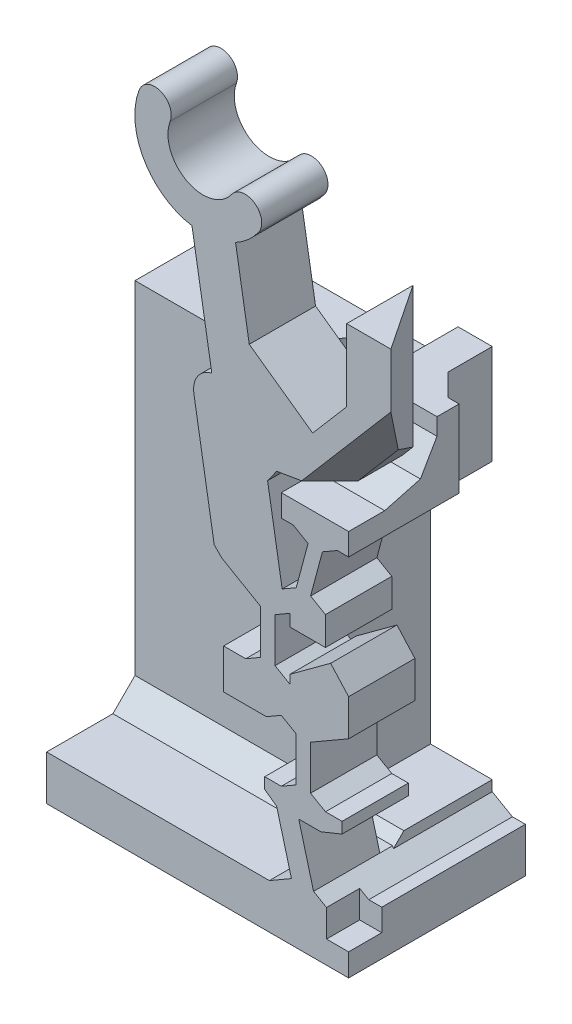
SolidWorks part; units mm, degrees
material "Nylon 6/12"
ref_plane "Front Plane" through (0, 0, 0) normal (0, 0, 1) x (1, 0, 0)
ref_plane "Top Plane" through (0, 0, 0) normal (0, 1, 0) x (1, 0, 0)
ref_plane "Right Plane" through (0, 0, 0) normal (1, 0, 0) x (0, 0, -1)
sketch "Sketch-SkeletonConfigUp" plane through (0, 0, 0) normal (0, 0, 1) x (1, 0, 0)
  line L0 (0, 0) -> (0, -50000) construction
  line L1 (0, 0) -> (4.5811, 6.2164) construction
  line L2 (9.8143, 13.3177) -> (4.5811, 13.945) construction
  line L3 (4.5811, 13.945) -> (2.9713, 10.4094) construction
  line L4 (2.9713, 10.4094) -> (4.5811, 6.2164) construction
  line L5 (4.5811, 13.945) -> (6.2429, 19.1409) construction
  line L6 (2.9713, 10.4094) -> (0.0405, 27.8193) construction
  line L7 (4.5811, 6.2164) -> (9.8143, 13.3177) construction
  line L8 (-587.3593, -797.0242) -> (9.8143, 13.3177) construction
  dimension "D2" = 7.7221
  dimension "D3" = 8.8212
  dimension "D4" = 5.2707
  dimension "D5" = 119.553
  dimension "D6" = 3.8848
  dimension "D7" = 5.4552
  dimension "D8" = 17.6549
  dimension "D9" = 4.4914
  dimension "D10" = 6.745
  dimension "D11" = 145.964
  dimension "D12" = 143.612
sketch "Sketch-SkeletonConfigDown" plane through (0, 0, 0) normal (0, 0, 1) x (1, 0, 0)
  line L0 (0, 0) -> (0, -50000) construction
  line L1 (0, 0) -> (4.5811, 6.2164) construction
  line L2 (9.8143, 13.3177) -> (4.5811, 13.945) construction
  line L3 (4.5811, 13.945) -> (6.1909, 10.4094) construction
  line L4 (6.1909, 10.4094) -> (4.5811, 6.2164) construction
  line L5 (4.5811, 13.945) -> (1.753, 18.6098) construction
  line L6 (6.1909, 10.4094) -> (-8.8652, 19.6294) construction
  line L7 (4.5811, 6.2164) -> (9.8143, 13.3177) construction
  line L8 (-589.9357, -800.5203) -> (9.8143, 13.3177) construction
  dimension "D2" = 7.7221
  dimension "D3" = 8.8212
  dimension "D4" = 5.2707
  dimension "D5" = 119.553
  dimension "D6" = 3.8848
  dimension "D7" = 5.4552
  dimension "D8" = 17.6549
  dimension "D9" = 4.4914
  dimension "D10" = 6.745
  dimension "D11" = 145.964
  dimension "D1" = 143.612
ref_plane "Plane-Cam Base" through (9.128, 0, 0) normal (1, 0, 0) x (0, 0, -1)
ref_plane "Plane-Down-to-Up Derailleur Clearance" through (6.628, 0, 0) normal (1, 0, 0) x (0, 0, -1)
ref_plane "Plane-Cam Cavity Roof" through (5.128, 0, 0) normal (1, 0, 0) x (0, 0, -1)
sketch "Sketch-SwitchBossUp" plane through (0, 0, 0) normal (0, 0, 1) x (1, 0, 0)
  line L0 (3.5811, 11.4759) -> (3.5811, 12.945) construction
  line L2 (6.5405, 21.1774) -> (6.5405, 24.4384)
  line L3 (6.5405, 24.4384) -> (8.5405, 24.4384)
  line L4 (8.5405, 24.4384) -> (8.5405, 20.4384)
  line L5 (5.5811, 12.5552) -> (5.5811, 11.263)
  line L7 (1.5115, 25.1048) -> (2.5464, 18.9575)
  line L8 (-0.4607, 24.7728) -> (0.4359, 19.4465)
  line L9 (2.9713, 10.4094) -> (0.0405, 27.8193) construction
  line L11 (-0.0396, 22.2712) -> (1.9326, 22.6032) construction
  line L15 (6.628, -23.7286) -> (6.628, 23.7286) construction
  line L16 (2.9713, 10.4094) -> (4.5811, 6.2164) construction
  line L17 (3.5811, 12.945) -> (3.5811, 14.945) construction
  line L18 (5.5811, 12.945) -> (5.5811, 14.945) construction
  line L19 (4.2561, 13.945) -> (4.9061, 13.945) construction
  line L20 (3.5811, 14.945) -> (5.5811, 14.945) construction
  line L21 (3.5811, 12.945) -> (5.5811, 12.945) construction
  line L22 (4.5811, 12.945) -> (4.5811, 14.945) construction
  line L23 (4.5811, 6.2164) -> (8.5405, 7.1023) construction
  line L24 (1.9713, 9.4094) -> (1.9713, 11.4094) construction
  line L25 (3.9713, 9.4094) -> (3.9713, 11.4094) construction
  line L26 (3.9713, 9.4094) -> (1.9713, 9.4094) construction
  line L27 (1.9713, 11.4094) -> (3.9713, 11.4094) construction
  line L28 (3.5811, 7.2164) -> (5.5811, 7.2164) construction
  line L29 (3.5811, 7.2164) -> (3.5811, 5.2164) construction
  line L30 (5.5811, 7.2164) -> (5.5811, 5.2164) construction
  line L31 (3.5811, 5.2164) -> (5.5811, 5.2164) construction
  line L32 (4.9061, 6.2164) -> (4.2561, 6.2164) construction
  line L40 (3.2963, 10.4094) -> (2.6463, 10.4094) construction
  line L43 (2.874, 4.5093) -> (0.7934, 4.5093) construction
  line L51 (4.9929, 19.3693) -> (2.5464, 18.9575)
  line L66 (0.0405, 27.8193) -> (0.0405, 50027.8193) construction
  line L74 (0.5455, 12.7717) -> (-0.3728, 18.2264)
  line L75 (0.3841, 13.7302) -> (2.3564, 14.0622) construction
  line L76 (5.5811, 11.263) -> (5.5811, 12.5552) construction
  line L77 (5.5811, 7.6061) -> (6.628, 8.2105)
  line L80 (5.8152, 10.763) -> (6.628, 9.8603)
  line L81 (8.5405, 1033.6218) -> (8.5405, 20.4384) construction
  line L82 (2.5464, 18.9575) -> (3.5585, 12.945) construction
  line L83 (3.6203, 12.5779) -> (2.8784, 16.9852)
  line L84 (2.8784, 16.9852) -> (6.0405, 17.5175)
  line L85 (6.9307, 9.5241) -> (8.5405, 7.7363) construction
  line L88 (3.5811, 16.3347) -> (6.8573, 16.3347)
  line L92 (3.7762, 8.3129) -> (6.9307, 9.5241) construction
  line L93 (6.3311, 4.3267) -> (5.3706, 3.937)
  line L95 (2.5464, 18.9575) -> (2.8784, 16.9852) construction
  line L96 (2.7124, 17.9713) -> (8.5405, 18.9524) construction
  line L97 (2.7124, 17.9713) -> (1.7262, 17.8053) construction
  line L98 (1.9713, 9.0197) -> (0.9713, 9.0197)
  line L99 (0.9713, 9.0197) -> (0.9713, 7.2164)
  line L100 (0.9713, 7.2164) -> (2.9061, 7.2164)
  line L101 (4.5811, 6.2164) -> (6.9307, 9.5241) construction
  line L103 (0.0405, 27.8193) -> (1.9448, 26.4638) construction
  line L104 (6.9307, 9.5241) -> (8.5405, 7.7363) construction
  line L106 (13.4416, 14.945) -> (5.5811, 14.945) construction
  line L107 (1.9713, 9.4094) -> (1.9713, 9.0197) construction
  line L109 (0.0405, 27.8193) -> (-2.1498, 28.6358) construction
  line L110 (8.5405, 20.4384) -> (6.0405, 17.5175)
  line L111 (6.628, 9.8603) -> (6.628, 8.2105)
  line L112 (6.628, 9.8603) -> (6.9307, 9.5241) construction
  line L113 (2.8311, 4.8267) -> (2.8311, 4.3267)
  line L114 (7.3693, 7.7363) -> (7.3563, 7.7363) construction
  line L115 (6.8573, 16.3347) -> (13.4416, 16.3347)
  line L116 (13.4416, 16.3347) -> (13.4416, -1.1653)
  line L117 (13.4416, -1.1653) -> (5.0405, -1.1653)
  line L119 (10.4375, 14.0252) -> (10.4375, 2.1692)
  line L121 (5.0405, -1.1653) -> (5.0405, 1.437) construction
  line L122 (8.237, 12.8031) -> (10.8393, 12.8031) construction
  line L123 (10.8393, 12.8031) -> (13.4416, 12.8031) construction
  line L124 (10.4375, 2.1692) -> (9.128, 0.8597)
  line L125 (8.5405, 7.5847) -> (13.4416, 7.5847) construction
  line L127 (5.5811, 15.3347) -> (5.5811, 14.945) construction
  line L130 (6.0405, 0.8597) -> (9.128, 0.8597)
  line L132 (2.8311, 4.3267) -> (3.3706, 3.937)
  line L133 (2.9713, 10.4094) -> (6.1909, 10.4094) construction
  line L134 (4.5811, 10.4094) -> (4.5811, 13.945) construction
  line L135 (4.5811, 10.4094) -> (4.5811, 6.2164) construction
  line L136 (0.8973, 12.4192) -> (0.5455, 12.7717)
  line L137 (3.9713, 9.4094) -> (5.5811, 7.2164) construction
  line L139 (5.8152, 10.763) -> (3.9713, 9.4094)
  line L141 (4.0405, 1.437) -> (3.0405, 0.8597)
  line L142 (3.0405, 0.8597) -> (3.0405, -1.1653)
  line L143 (8.5405, 20.4384) -> (8.5405, 18.9524) construction
  line L145 (8.5405, 17.9384) -> (8.5405, -49992.0368) construction
  line L147 (5.5811, 11.263) -> (5.5811, 12.5552) construction
  line L149 (6.3311, 4.8267) -> (6.3311, 4.3267)
  line L150 (3.0405, -1.1653) -> (5.0405, -1.1653)
  line L151 (3.3706, 3.937) -> (5.3706, 3.937) construction
  line L152 (4.792, 14.945) -> (4.2561, 12.945)
  line L153 (5.442, 14.945) -> (4.9061, 12.945)
  line L157 (3.5811, 16.3347) -> (3.5811, 15.3347)
  line L158 (6.117, 15.3347) -> (9.128, 15.3347)
  line L162 (3.2963, 11.4094) -> (3.2963, 9.4094)
  line L164 (2.6463, 11.4094) -> (2.6463, 9.4094)
  line L169 (4.2561, 7.2164) -> (4.2561, 5.2164)
  line L170 (4.9061, 5.2164) -> (4.9061, 7.2164)
  line L175 (4.2561, 7.2164) -> (3.5811, 7.6061)
  line L176 (4.9061, 7.2164) -> (5.5811, 7.6061)
  line L177 (5.5811, 7.2164) -> (5.5811, 7.6061) construction
  line L179 (4.2561, 5.2164) -> (3.5811, 4.8267)
  line L180 (3.5811, 5.2164) -> (3.5811, 4.8267) construction
  line L181 (3.5811, 4.8267) -> (2.8311, 4.8267)
  line L183 (4.9061, 5.2164) -> (5.5811, 4.8267)
  line L184 (5.5811, 5.2164) -> (5.5811, 4.8267) construction
  line L186 (9.128, -23.7286) -> (9.128, 23.7286) construction
  line L187 (2.6463, 9.4094) -> (1.9713, 9.0197)
  line L188 (3.2963, 9.4094) -> (3.9713, 9.0197)
  line L189 (3.2963, 11.4094) -> (3.9713, 11.7991)
  line L190 (2.6463, 11.4094) -> (0.8973, 12.4192)
  line L191 (3.9713, 11.4094) -> (3.9713, 11.7991) construction
  line L192 (3.9713, 11.7991) -> (3.9713, 11.263)
  line L193 (4.9061, 12.945) -> (5.5811, 12.5552)
  line L194 (4.2561, 12.945) -> (3.6203, 12.5779)
  line L195 (3.9713, 11.263) -> (5.5811, 11.263)
  line L196 (3.9713, 9.4094) -> (3.9713, 9.0197)
  line L197 (3.5811, 7.2164) -> (3.5811, 7.6061) construction
  line L199 (3.5811, 7.6061) -> (2.9061, 7.2164)
  line L200 (5.5811, 4.8267) -> (6.3311, 4.8267)
  line L201 (2.8311, 4.3267) -> (2.8311, 3.937) construction
  line L202 (2.8311, 3.937) -> (3.3706, 3.937) construction
  line L203 (10.4375, 14.0252) -> (9.128, 15.3347)
  line L204 (5.0405, 1.437) -> (3.0405, 1.437) construction
  line L205 (3.0405, 1.437) -> (3.0405, 0.8597) construction
  line L206 (5.0405, 1.437) -> (6.0405, 0.8597)
  line L207 (8.5405, 18.9524) -> (8.5405, 17.9384) construction
  line L208 (6.0405, 17.5175) -> (8.5405, 17.9384) construction
  line L209 (8.5405, 20.4384) -> (8.5405, 17.9384) construction
  line L210 (6.5405, 21.1774) -> (4.9929, 19.3693)
  line L211 (5.0405, 1.437) -> (4.3706, 3.937)
  line L212 (4.0405, 1.437) -> (3.3706, 3.937)
  line L213 (5.3706, 3.937) -> (4.3706, 3.937)
  line L214 (4.792, 14.945) -> (4.1169, 15.3347)
  line L215 (4.1169, 15.3347) -> (3.5811, 15.3347)
  line L216 (5.442, 14.945) -> (6.117, 15.3347)
  line L217 (5.5811, 12.945) -> (5.5811, 12.5552) construction
  line L218 (5.442, 14.945) -> (5.442, 15.3347) construction
  line L219 (6.117, 15.3347) -> (4.1169, 15.3347) construction
  arc A0 (1.5115, 25.1048) -> (2.5558, 26.0289) centre (0.0405, 27.8193) ccw
  arc A1 (-0.4607, 24.7728) -> (-2.8525, 28.8978) centre (0.0405, 27.8193) cw
  arc A2 (-2.8525, 28.8978) -> (-1.447, 28.3738) centre (-2.1498, 28.6358) cw
  arc A3 (2.5558, 26.0289) -> (1.3338, 26.8987) centre (1.9448, 26.4638) ccw
  arc A4 (-1.447, 28.3738) -> (1.3338, 26.8987) centre (0.0405, 27.8193) ccw
  arc A5 (3.5811, 12.945) -> (3.5811, 14.945) centre (3.1778, 13.945) ccw construction
  arc A6 (5.5811, 12.945) -> (5.5811, 14.945) centre (5.9843, 13.945) cw construction
  arc A7 (2.5293, 9.921) -> (1.9713, 11.4094) centre (1.568, 10.4094) ccw construction
  arc A8 (3.9713, 11.4094) -> (3.9713, 9.4094) centre (4.3745, 10.4094) ccw construction
  arc A9 (3.5811, 7.2164) -> (3.5811, 5.2164) centre (3.1779, 6.2164) cw construction
  arc A10 (5.5811, 7.2164) -> (5.5811, 5.2164) centre (5.9844, 6.2164) ccw construction
  arc A19 (-0.3728, 18.2264) -> (0.4359, 19.4465) centre (0.6836, 18.4042) cw
  circle A28 centre (0.0405, 27.8193) radius 2.3375 construction
  arc A29 (1.9713, 9.4094) -> (2.5293, 9.921) centre (1.568, 10.4094) ccw construction
  point P53 (4.5811, 13.945)
  point P63 (2.9713, 10.4094)
  point P93 (0.9465, 22.4372)
  dimension "D23" = 1.5875
  dimension "D24" = 0.75
  dimension "D2" = 2
  dimension "D5" = 2
  dimension "D6" = 0.65
  dimension "D8" = 42
  dimension "D7" = 2
  dimension "D11" = 8.5
  dimension "D14" = 7.5
  dimension "D4" = 3
  dimension "D16" = 42
  dimension "D27" = 120
  dimension "D28" = 120
  dimension "D29" = 120
  dimension "D30" = 120
  dimension "D31" = 120
  dimension "D32" = 120
  dimension "D33" = 120
  dimension "D34" = 120
  dimension "D17" = 0.5
  dimension "D20" = 3.5
  dimension "D21" = 1
  dimension "D18" = 45
  dimension "D9" = 17.5
  dimension "D22" = 1
  dimension "D15" = 45
  dimension "D38" = 2
  dimension "D39" = 0.5
  dimension "D40" = 60
  dimension "D41" = 1
  dimension "D42" = 45
  dimension "D43" = 120
  dimension "D44" = 2
  dimension "D45" = 2.5
  dimension "D46" = 2.5
  dimension "D47" = 4
  dimension "D48" = 2
  dimension "D10" = 15
  dimension "D12" = 2.5
  dimension "D13" = 1
  dimension "D19" = 1
  dimension "D25" = 15
  dimension "D26" = 120
  dimension "D35" = 120
extrude "Boss-Switch Body" add sketch "Sketch-SwitchBossUp" along normal blind 3
sketch "Sketch1" plane through (0, 0, 0) normal (0, 0, -1) x (-1, 0, 0)
  line L1 (-7.5811, -1.1653) -> (0.4122, -1.1653)
  line L2 (-7.5811, -1.1653) -> (-7.5811, 0.8597)
  line L4 (0.4122, -1.1653) -> (0.4122, 0.8597)
  line L5 (-3.5811, 18.8347) -> (-7.5811, 18.8347)
  line L10 (-7.5811, 18.8347) -> (-7.5811, 15.3347)
  line L11 (-4.0405, 1.437) -> (-5.0405, 1.437)
  line L12 (-7.5811, 15.3347) -> (-3.5811, 15.3347)
  line L13 (-4.0405, 1.437) -> (-3.0405, 0.8597)
  line L14 (-3.5811, 15.3347) -> (-3.5811, 18.8347)
  line L20 (-4.3706, 3.937) -> (-5.0405, 1.437) construction
  line L22 (-3.0405, -1.1653) -> (-13.4416, -1.1653) construction
  line L23 (-3.0405, 0.8597) -> (0.4122, 0.8597)
  line L24 (-5.0405, 1.437) -> (-6.0405, 0.8597)
  line L25 (-6.0405, 0.8597) -> (-7.5811, 0.8597)
  line L27 (-3.5811, 16.3347) -> (-3.5811, 15.3347) construction
  dimension "D1" = 3.5
  dimension "D4" = 4
extrude "Boss-Flange Width" add sketch "Sketch1" along normal blind 5
ref_plane "Plane-Sta2Sit Groove" through (0.0405, 0, 0) normal (1, 0, 0) x (0, 0, -1)
ref_plane "Plane-Cam Outer Surface" through (-12.0395, 0, 0) normal (1, 0, 0) x (0, 0, -1)
ref_plane "Plane-FlangeTop" through (-7.0395, 0, 0) normal (1, 0, 0) x (0, 0, -1)
sketch "Sketch2" plane through (-7.0395, 0, 0) normal (1, 0, 0) x (0, 0, -1)
  line L0 (5, 15.3347) -> (-3, 15.3347) construction
  line L1 (5, 17.3347) -> (1, 17.3347)
  line L2 (5, 17.3347) -> (5, 15.3347)
  line L3 (5, 15.3347) -> (1, 15.3347)
  line L4 (1, 17.3347) -> (1, 15.3347)
  line L10 (-3, -1.1653) -> (-3, 16.3347) construction
  line L11 (5, 0.8597) -> (-3, 0.8597)
  line L12 (5, 0.8597) -> (5, -1.1653)
  line L13 (5, -1.1653) -> (-3, -1.1653)
  line L14 (-3, 0.8597) -> (-3, -1.1653)
  line L15 (0, 10.4094) -> (0, 27.8193) construction
  line L17 (5, 0.8597) -> (5, -1.1653) construction
  line L18 (-3, 0.8597) -> (0, 0.8597) construction
  dimension "D1" = 1
  dimension "D2" = 2
extrude "Boss-Flange Height" add sketch "Sketch2" along normal up to surface (11.6675 mm away)
sketch "Sketch10" plane through (0, 15.3347, 0) normal (0, 1, 0) x (1, 0, 0)
  line L0 (9.128, -23.7286) -> (9.128, 23.7286) construction
  line L1 (7.5811, 5) -> (5.128, 5)
  line L2 (7.5811, 5) -> (7.5811, 2)
  line L3 (7.5811, 2) -> (5.128, 2)
  line L5 (4.628, 7) -> (4.628, 1) construction
  line L6 (3.5811, 1) -> (-7.0395, 1) construction
  line L8 (5.128, 5) -> (5.128, 2)
  dimension "D1" = 1
  dimension "D2" = 0.5
  dimension "D3" = 4.5
extrude "Cut-Up-To-Down Derailleur Clearance" cut sketch "Sketch10" along normal up to next
sketch "Sketch17" plane through (0, 15.3347, 0) normal (0, -1, 0) x (1, 0, 0)
  line L0 (5.128, -5) -> (-7.0395, -5)
  line L1 (5.128, -5) -> (-7.0395, -5) construction
  line L2 (-7.0395, -5) -> (-7.0395, -1)
  line L3 (-7.0395, -1) -> (5.128, -1)
  line L4 (5.128, -1) -> (5.128, -5)
  line L5 (-7.0395, -1) -> (-7.0395, -5) construction
extrude "Boss-Flange Support" add sketch "Sketch17" along normal up to surface (14.475 mm away) up to face at (-1.9995, 0.8597, -1)
sketch "Sketch-HolePositions" plane through (0, -1.1653, 0) normal (0, -1, 0) x (1, 0, 0)
  line L0 (-7.0395, -3) -> (7.5811, -3) construction
  line L1 (7.5811, -5) -> (-7.0395, -5) construction
  line L2 (7.5811, -5) -> (7.5811, 0) construction
  line L4 (-7.0395, -22.2167) -> (-7.0395, 22.2167) construction
  line L5 (3.5811, -1) -> (3.5811, -5) construction
  point P6 (-4.0395, -3)
  point P7 (0.5811, -3)
  dimension "D1" = 3
  dimension "D2" = 3
  dimension "D3" = 2
sketch "Sketch6" plane through (0, -1.1653, 0) normal (0, -1, 0) x (-1, 0, 0)
  point P0 (4.0395, 3)
  point P3 (-0.5811, 3)
hole_wizard "Tap Drill for M2x0.4 Tap1" positions "Sketch6" profile "Sketch5" hole size "M2x0.4" standard "ANSI Metric" end condition through all
sketch "Sketch5" plane through (-4.0395, -1.1653, -3) normal (1, 0, 0) x (0, 0, -1)
  line L0 (0, 0) -> (0, 30.5511)
  line L1 (0, 30.5511) -> (0.8, 30.5511)
  line L2 (0.8, 30.5511) -> (0.8, 0)
  line L5 (0.8, 0) -> (0, 0)
  line L11 (0, -6.35) -> (0, 107.95) construction
  dimension "Thru Hole Dia." = 1.6
  dimension "Thru Hole Depth" = 30.5511
sketch "Sketch9" plane through (0, -1.1653, 0) normal (0, -1, 0) x (1, 0, 0)
  point P0 (-4.0395, -3)
  point P3 (0.5811, -3)
hole_wizard "M2 Clearance Hole2" positions "Sketch9" profile "Sketch8" hole size "M2" standard "ANSI Metric"
sketch "Sketch8" plane through (-4.0395, -1.1653, -3) normal (1, 0, 0) x (0, 0, -1)
  line L0 (0, 0) -> (0, 15.721)
  line L1 (0, 15.721) -> (1.2, 15)
  line L2 (1.2, 15) -> (1.2, 0)
  line L5 (1.2, 0) -> (0, 0)
  line L10 (0, 15.721) -> (-1.2, 15) construction
  line L11 (0, -6.35) -> (0, 107.95) construction
  dimension "Hole Dia." = 2.4
  dimension "Hole Depth" = 15
  dimension "Drill Angle" = 118
sketch "Sketch-Measurements for Derailleur Ramps" plane through (0, 0, 0) normal (0, 0, 1) x (1, 0, 0)
  line L0 (2.8784, 16.9852) -> (2.5464, 18.9575)
  line L1 (2.7124, 17.9713) -> (1.7262, 17.8053)
  line L2 (2.9713, 10.4094) -> (0.0405, 27.8193) construction
  line L3 (1.7262, 17.8053) -> (-1.8937, 15.3603)
  line L4 (6.1909, 10.4094) -> (-8.8652, 19.6294) construction
  line L5 (1.7262, 17.8053) -> (2.6012, 12.6077)
  line L6 (2.6012, 12.6077) -> (-1.8937, 15.3603)
  line L7 (-0.0837, 16.5828) -> (-0.0837, 17.8053)
  line L8 (-0.0837, 17.8053) -> (1.7262, 17.8053)
  line L9 (6.1909, 10.4094) -> (2.9713, 10.4094)
  line L10 (5.386, 8.3129) -> (3.7762, 8.3129)
  line L12 (6.1909, 10.4094) -> (4.5811, 6.2164) construction
  line L13 (4.5811, 8.3129) -> (4.5811, 8.7912)
  line L14 (4.5811, 6.2164) -> (5.386, 8.3129)
  line L15 (2.9713, 10.4094) -> (4.5811, 6.2164) construction
  line L16 (3.7762, 8.3129) -> (4.5811, 6.2164)
  line L17 (5.386, 8.3129) -> (5.386, 8.7912)
  dimension "D1" = 1.81
  dimension "D2" = 0.8049
sketch "Sketch12" plane through (0, 24.4384, 0) normal (0, 1, 0) x (1, 0, 0)
  line L0 (6.5405, 0) -> (8.5405, -3)
  line L1 (8.5405, -3) -> (8.5405, 0)
  line L2 (8.5405, 0) -> (6.5405, 0)
extrude "Cut-Up-to-Down Cantilever Slope" cut sketch "Sketch12" against normal up to next
ref_plane "Plane1" through (0, 7.1023, 0) normal (0, 1, 0) x (1, 0, 0)
sketch "Sketch-Derailleur Location" plane through (0, 7.1023, 0) normal (0, 1, 0) x (1, 0, 0)
  line L0 (8.5405, 0) -> (8.5405, -3)
  line L1 (4.0405, -3) -> (3.0405, -3) construction
  line L2 (-119237.4187, 0) -> (9.8143, 0) construction
  point P0 (8.5405, 0)
  point P8 (8.5405, -1.5)
ref_plane "Plane-Cantilever Cut" [suppressed] through (7.0848, 8.5204, -1.9058) normal (-0.6301, -0.7578, 0.1695) x (-0.7765, 0.6151, -0.1368)
sketch "Sketch14" [suppressed] plane through (7.0848, 8.5204, -1.9058) normal (-0.6301, -0.7578, 0.1695) x (-0.7765, 0.6151, -0.1368)
  line L0 (2.3023, -1.6911) -> (-0.3551, -1.6911)
  line L2 (2.3023, -4.3362) -> (2.3023, -1.6911)
  line L3 (-0.3551, -1.6911) -> (-0.3551, -4.4608)
  line L5 (-0.3551, -4.4608) -> (1.0087, -5.0843)
  line L6 (1.0087, -5.0843) -> (2.3023, -4.3362)
extrude "Cut-Down-to-Up Cantilever Slope" [suppressed] cut sketch "Sketch14" against normal up to next
sketch "Sketch16" plane through (0, 0, 0) normal (0, 0, -1) x (-1, 0, 0)
  line L0 (-7.5811, 18.8347) -> (-13.4416, 18.8347)
  line L1 (-13.4416, 18.8347) -> (-13.4416, -1.1653)
  line L2 (-13.4416, -1.1653) -> (-6.628, -1.1653)
  line L3 (-13.4416, -1.1653) -> (-5.0405, -1.1653) construction
  line L4 (-6.628, -1.1653) -> (-6.628, 5.2038)
  line L5 (-6.628, 5.2038) -> (-8.0037, 5.2038)
  line L6 (-8.0037, 5.2038) -> (-8.0037, 12.0484)
  line L7 (-8.0037, 12.0484) -> (-6.628, 12.0484)
  line L8 (-6.628, 12.0484) -> (-6.628, 17.9477)
  line L9 (-6.628, 23.7286) -> (-6.628, -23.7286) construction
  line L10 (-3.5811, 18.8347) -> (-6.5405, 18.8347) construction
  line L11 (-7.5811, 18.8347) -> (-6.628, 17.9477)
extrude "Cut-Down-to-Up Derailleur Clearance" cut sketch "Sketch16" against normal through all and the other way through all
ref_plane "Plane-Symmetry Plane" through (0, 0, 1.5) normal (0, 0, 1) x (1, 0, 0)
sketch "Sketch-Cable Center Point" plane through (0, 0, 1.5) normal (0, 0, 1) x (1, 0, 0)
  line L0 (0.0405, 27.8193) -> (0.1722, 27.0366)
  line L1 (2.9713, 10.4094) -> (0.0405, 27.8193) construction
  point P0 (0.0405, 27.8193)
  dimension "D1" = 0.7937
chamfer "Chamfer-Flange Support" distance 1.5 angle 45 1 edges at (3.5811, 17.3347, -3)
chamfer "Chamfer-Flange Support 2" distance 1 angle 45 2 edges at (5.128, 17.0847, -2) (5.128, 15.3347, -1.5)
chamfer "Chamfer-Flange Support 3" distance 1 angle 45 1 edges at (-1.9995, 0.8597, -1)
sketch "Sketch18" plane through (6.628, 0, 0) normal (1, 0, 0) x (0, 0, -1)
  line L1 (-3, -0.1403) -> (-1.5, -0.1403)
  line L2 (-3, -0.1403) -> (-3, 1.437)
  line L3 (-3, 1.437) -> (-1.5, 1.437)
  line L4 (-1.5, -0.1403) -> (-1.5, 1.437)
  line L5 (0.5774, 1.437) -> (0, 1.437) construction
  line L6 (-3, -1.1653) -> (-3, 0.8597) construction
  line L7 (-3, 0.8597) -> (5, 0.8597) construction
  dimension "D1" = 1.5
  dimension "D2" = 1
extrude "Cut-Down-to-Up Derailleur Clearance 2" cut sketch "Sketch18" against normal blind 1
sketch "Sketch19" plane through (0, 0, 0) normal (0, 0, 1) x (1, 0, 0)
  line L7 (3.5811, 18.8983) -> (6.628, 18.8983)
  line L8 (6.628, 18.8983) -> (6.628, 16.3347)
  line L9 (6.628, 16.3347) -> (3.5811, 16.3347)
  line L10 (3.5811, 16.3347) -> (3.5811, 18.8983)
  line L11 (6.628, 16.3347) -> (6.628, 17.9477) construction
extrude "Cut-Up-to-Down Cantilever Clearance" cut sketch "Sketch19" against normal up to surface (1 mm away) up to face at (1.4435, 12.7784, -1)
chamfer "Chamfer1" distance 1 angle 60 1 edges at (5.1045, 16.3347, -1) first distance on face at (5.1045, 16.3347, 1)
chamfer "Chamfer3" distance 0.75 angle 60 1 edges at (3.5811, 16.7007, -1) first distance on face at (3.5811, 16.2811, 0.8)
chamfer "Chamfer4" distance 0.5 angle 60 1 edges at (4.205, 15.3347, -1) first distance on face at (5.0385, 15.3347, 0.5227)
chamfer "Chamfer5" distance 0.5 angle 45 1 edges at (2.8784, 16.9852, 1.5)
chamfer "Chamfer6" distance 2.5 angle 45 1 edges at (2.5464, 18.9575, 1.5)
chamfer "Chamfer7" distance 1 angle 45 1 edges at (7.2905, 18.978, 3)
sketch "Sketch22" plane through (0, 0, 0) normal (0, 0, 1) x (1, 0, 0)
  line L0 (6.628, 17.9477) -> (7.5811, 18.8347) construction
  line L1 (6.628, 18.8347) -> (7.5811, 18.8347) construction
  line L2 (6.628, 17.9477) -> (6.628, 18.8347) construction
  line L3 (6.628, 17.9477) -> (7.5811, 18.8347)
  line L4 (6.628, 18.8347) -> (7.5811, 18.8347)
  line L5 (6.628, 17.9477) -> (6.628, 18.8347)
extrude "Cut-Extrude3" cut sketch "Sketch22" against normal up to next
chamfer "Chamfer8" distance 0.5 angle 45 1 edges at (5.1045, 16.3347, 0) first distance on face at (4.2965, 17.2286, -0.5161)
sketch "Sketch23" plane through (0, 0, -1) normal (0, 0, 1) x (1, 0, 0)
  line L0 (5.128, 1.8597) -> (2.3369, 1.8597)
  line L1 (-7.0395, 1.8597) -> (5.128, 1.8597) construction
  line L2 (2.3369, 1.8597) -> (2.3369, 14.3347)
  line L3 (2.3369, 14.3347) -> (5.128, 14.3347)
  line L4 (5.128, 14.3347) -> (5.128, 1.8597)
extrude "Cut-Extrude4" cut sketch "Sketch23" against normal through all
equation "\"axle-diameter\"=2"
equation "\"switch-thickness\"=12"
equation "\"base-width\"=4.0"
equation "\"axle-bushing-radius\"=3"
equation "\"clearance\"= 0.25"
equation "\"arm-width\"=1.5"
equation "\"min-diameter\"=70"
equation "\"alpha\"=143.6120"
equation "\"gamma\"=119.5526"
equation "\"delta\"=145.9637"
equation "\"epsilon\"=6.7452"
equation "\"l_AB\"=8.8212"
equation "\"l_AC\"=4.4914"
equation "\"l_BD\"=5.2707"
equation "\"l_CD\"=3.8848"
equation "\"l_CE\"=17.6549"
equation "\"l_DF\"=5.4552"
equation "\"l_OA\"=7.7221"
equation "\"D2@Sketch-SkeletonConfigUp\" = \"l_OA\""
equation "\"D3@Sketch-SkeletonConfigUp\" = \"l_AB\""
equation "\"D4@Sketch-SkeletonConfigUp\" = \"l_BD\""
equation "\"D5@Sketch-SkeletonConfigUp\" = \"gamma\""
equation "\"D6@Sketch-SkeletonConfigUp\" = \"l_CD\""
equation "\"D7@Sketch-SkeletonConfigUp\" = \"l_DF\""
equation "\"D8@Sketch-SkeletonConfigUp\" = \"l_CE\""
equation "\"D9@Sketch-SkeletonConfigUp\" = \"l_AC\""
equation "\"D_groove\"=3.175"
equation "\"D7@Sketch-SkeletonConfigDown\" = \"l_DF\""
equation "\"D6@Sketch-SkeletonConfigDown\" = \"l_CD\""
equation "\"D2@Sketch-SkeletonConfigDown\" = \"l_OA\""
equation "\"D3@Sketch-SkeletonConfigDown\" = \"l_AB\""
equation "\"D9@Sketch-SkeletonConfigDown\" = \"l_AC\""
equation "\"D8@Sketch-SkeletonConfigDown\" = \"l_CE\""
equation "\"D5@Sketch-SkeletonConfigDown\" = \"gamma\""
equation "\"D4@Sketch-SkeletonConfigDown\" = \"l_BD\""
equation "\"D1@Sketch-SkeletonConfigDown\" = \"alpha\""
equation "\"hinge_length\"=1.5"
equation "\"hinge_depth\"=0.25"
equation "\"D10@Sketch-SkeletonConfigUp\"=\"epsilon\""
equation "\"D11@Sketch-SkeletonConfigUp\"=\"delta\""
equation "\"D12@Sketch-SkeletonConfigUp\"=\"alpha\""
equation "\"D11@Sketch-SkeletonConfigDown\"=\"delta\""
equation "\"D10@Sketch-SkeletonConfigDown\"=\"epsilon\""
equation "\"EE_dx\"=8.9056"
equation "\"EE_dy\"=8.1898"
equation "\"r_groove\"=\"D_groove\"/2"
equation "\"t_wall\"=25.4/16"
equation "\"width_lower\"=\"D_groove\"+\"t_wall\""
equation "\"cable_to_bottom\"=30.6257"
equation "\"switch_EE-up_base_dy\"=24"
equation "\"switch_EE-down_base_dy\"=16"
equation "\"D_axle\"=25.4/8"
equation "\"D_up_to_down\"=16"
equation "\"D_down_to_up\"=25"
equation "\"t_cam_base\"=7.5"
equation "\"D23@Sketch-SwitchBossUp\"=\"D_groove\"/2"
equation "\"D1@Sketch-Cable Center Point\"=\"D_groove\"/4"
